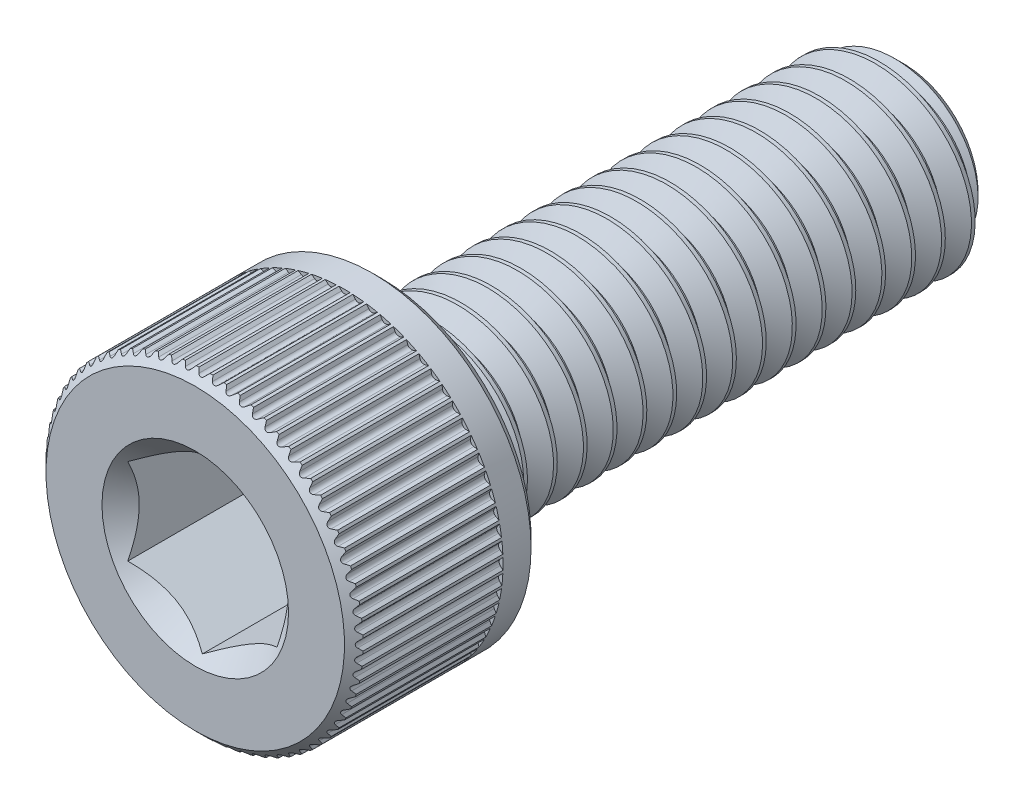
SolidWorks part; units mm, degrees
ref_plane "Front Plane" through (0, 0, 0) normal (0, 0, 1) x (1, 0, 0)
ref_plane "Top Plane" through (0, 0, 0) normal (0, 1, 0) x (1, 0, 0)
ref_plane "Right Plane" through (0, 0, 0) normal (1, 0, 0) x (0, 0, -1)
sketch "Sketch1" plane through (0, 0, 0) normal (1, 0, 0) x (0, 0, -1)
  line L0 (-9.5, 0) -> (9.5, 0) construction
  line L1 (9.5, 0) -> (9.5, 1.9804) construction
  line L2 (9.5, 1.9804) -> (8.9804, 2.5) construction
  line L3 (8.9804, 2.5) -> (8.9, 2.5) construction
  line L4 (8.9, 2.5) -> (-4.5, 2.5) construction
  line L5 (-4.5, 2.5) -> (-4.5, 4.25) construction
  line L6 (-4.5, 4.25) -> (-9.5, 4.25) construction
  line L7 (-9.5, 4.25) -> (-9.5, 0) construction
  line L8 (9.5, 1.9804) -> (9.5, 2.5) construction
  line L9 (9.45, 2.5866) -> (9.85, 1.8938) construction
  line L10 (9.85, 1.8938) -> (10.25, 2.5866) construction
  line L11 (10.25, 2.5866) -> (9.45, 2.5866) construction
  line L12 (9.85, 2.5866) -> (9.85, 2.5) construction
  line L13 (9.85, 1.8938) -> (9.85, 1.9804) construction
  line L14 (9.8, 1.9804) -> (9.9, 1.9804) construction
  line L15 (9.5, 2.5) -> (10.2, 2.5) construction
  line L16 (9.475, 2.5433) -> (10.225, 2.5433) construction
  line L17 (9.5, 0) -> (9.5, -2.5) construction
  line L18 (-4.75, 4.25) -> (-4.5, 4) construction
  line L19 (-9.25, 4.25) -> (-9.5, 4) construction
  line L20 (-4.5, 2.5) -> (-4.5, 0) construction
  line L21 (-4.5, 1.25) -> (0.1667, 1.25) construction
  line L22 (0.1667, 1.25) -> (4.8333, 1.25) construction
  line L23 (4.8333, 1.25) -> (9.5, 1.25) construction
  line L24 (0.1667, 1.25) -> (0.1667, 2.5) construction
  line L25 (0.1667, 2.5) -> (0.1667, 4.25) construction
  line L26 (4.8333, 1.25) -> (4.8333, 4.25) construction
  point P0 (-9.5, 2)
  point P3 (7.5, 2.5)
  point P4 (0, 0)
  point P18 (4.8333, 2.5)
  point P22 (9.85, 1.9804)
  point P24 (8.9, 2.5)
  point P25 (9.85, 2.5)
  point P28 (9.85, 2.5433)
  point P29 (7.5, -2.5)
  point P30 (0.1667, 2.5)
  point P31 (-7, 4.25)
  point P37 (-5.375, 4.25)
  point P38 (-9.125, 4.25)
  point P45 (0.1667, 1.25)
  point P46 (4.8333, 1.25)
  dimension "D7" = 0.25
  dimension "D8" = 0.25
  dimension "D9" = 0.25
  dimension "D10" = 0.125
  dimension "D11" = 0.625
  dimension "Drive Size" = 4
  dimension "Head Diameter" = 8.5
  dimension "Head Height" = 5
  dimension "Thread Pitch" = 0.8
  dimension "Thread Size" = 5
  dimension "Length" = 14
  dimension "D12" = 0.6
  dimension "D4" = 2
  dimension "D3" = 45
sketch "Sketch2" plane through (0, 0, 0) normal (1, 0, 0) x (0, 0, -1)
  line L0 (-9.5, 0) -> (-9.5, 4)
  line L1 (-9.25, 4.25) -> (-4.75, 4.25)
  line L2 (-4.5, 4) -> (-4.5, 2.75)
  line L4 (8.9804, 2.5) -> (9.5, 1.9804)
  line L5 (9.5, 1.9804) -> (9.5, 0)
  line L6 (-4.5, 4.25) -> (-9.5, 4.25) construction
  line L7 (9.5, 0) -> (-9.5, 0)
  line L8 (-9.25, 4.25) -> (-9.5, 4) construction
  line L10 (-9.25, 4.25) -> (-9.5, 4)
  line L14 (-4.75, 4.25) -> (-4.5, 4) construction
  line L16 (-4.75, 4.25) -> (-4.5, 4)
  line L17 (-4.5, 2.5) -> (-4.5, 4.25) construction
  line L19 (-4.25, 2.5) -> (8.9804, 2.5)
  line L20 (8.9, 2.5) -> (-4.5, 2.5) construction
  arc A1 (-4.5, 2.75) -> (-4.25, 2.5) centre (-4.25, 2.75) ccw
  dimension "D3" = 0.25
revolve "Revolve1" add sketch "Sketch2" angle 360 about L7
sketch "Sketch3" plane through (0, 0, 9.5) normal (0, 0, 1) x (1, 0, 0)
  line L1 (2, -1.1547) -> (2, 1.1547)
  line L2 (2, 1.1547) -> (0, 2.3094)
  line L3 (0, 2.3094) -> (-2, 1.1547)
  line L4 (-2, 1.1547) -> (-2, -1.1547)
  line L5 (-2, -1.1547) -> (0, -2.3094)
  line L6 (0, -2.3094) -> (2, -1.1547)
  circle A0 centre (0, 0) radius 2 construction
  circle A1 centre (0, 0) radius 4.25 construction
  circle A2 centre (0, 0) radius 4.25 construction
  circle A3 centre (0, 0) radius 2.3094 construction
  point P13 (0, 0)
extrude "Cut-Extrude1" cut sketch "Sketch3" against normal offset from surface (4 mm away) 1 up to face at (0, 4, 4.5)
sketch "Sketch4" plane through (0, 0, 9.5) normal (0, 0, 1) x (1, 0, 0)
  circle A0 centre (0, 0) radius 2.5
  dimension "D1" = 5
extrude "Cut-Extrude2" cut sketch "Sketch4" against normal up to vertex (2.5 mm away) draft 45 up to point (0, 4.25, 7)
sketch "Sketch11" plane through (0, 0, 0) normal (1, 0, 0) x (0, 0, -1)
  line L0 (-9.5, 0) -> (9.5, 0) construction
  line L1 (-9.5, 0) -> (9.5, 0) construction
  line L2 (-1.875, 0) -> (-1.875, 2.5) construction
  line L3 (8.9, 2.5) -> (-4.5, 2.5) construction
  line L4 (6.875, 0) -> (6.875, 2.5) construction
  line L6 (9.5, 1.9804) -> (9.5, 2.5) construction
  point P2 (-1.875, 0)
  point P3 (6.875, 0)
  dimension "D1" = 2.625
  dimension "D2" = 2.625
sketch "Sketch6" plane through (0, 0, -9.5) normal (0, 0, -1) x (-1, 0, 0)
  circle A0 centre (0, 0) radius 2.5
curve "Helix/Spiral1" pitch 0.8 height 14.8 radius 2.5 centre (0, 0, -9.5) axis (0, 0, 1) start towards (0, 1, 0)
sketch "Sketch10" plane through (0, 0, 0) normal (1, 0, 0) x (0, 0, -1)
  line L0 (-4.25, -4.25) -> (-4.25, 4.25)
  line L5 (-9.5, 0) -> (9.5, 0) construction
  line L6 (-4.25, 2.5) -> (-4.25, -2.5) construction
  point P3 (-4.25, 0)
split "Split1" trim tools "Sketch10" bodies to split 106 resulting bodies 114 115
sketch "Sketch7" plane through (0, 0, 0) normal (1, 0, 0) x (0, 0, -1)
  line L0 (9.475, 2.5433) -> (10.225, 2.5433)
  line L1 (10.225, 2.5433) -> (9.9, 1.9804)
  line L2 (9.9, 1.9804) -> (9.8, 1.9804)
  line L3 (9.8, 1.9804) -> (9.475, 2.5433)
sweep "Cut-Sweep1" cut profiles "Sketch7" path "Helix/Spiral1" align with end faces yes
sketch "Sketch8" plane through (0, 0, 0) normal (1, 0, 0) x (0, 0, -1)
  line L0 (-4.5, 0) -> (-4.5, 2.5)
  line L1 (-4.25, -2.5) -> (-4.25, 2.5) construction
  line L2 (-4.5, 2.5) -> (-4.25, 2.5)
  line L4 (-4.25, 2.5) -> (-2.8066, 0)
  line L5 (-2.8066, 0) -> (-4.5, 0)
  line L6 (8.9, 2.5) -> (-4.5, 2.5) construction
  line L7 (-9.5, 0) -> (9.5, 0) construction
  dimension "D1" = 60
revolve "Revolve2" add sketch "Sketch8" angle 360 about L5
ref_plane "Plane1" through (0, 0, 9.5) normal (0, 0, 1) x (1, 0, 0)
sketch "Sketch12" plane through (0, 0, 9.5) normal (0, 0, 1) x (1, 0, 0)
  line L0 (0, 0) -> (0.1483, 4.2474) construction
  line L1 (0, 0) -> (-0.1483, 4.2474) construction
  line L2 (0, 4.1437) -> (0, 4.3563) construction
  line L3 (-0.2572, 4.3563) -> (0.2572, 4.3563)
  line L4 (-0.2572, 4.3563) -> (-0.0762, 4.1753)
  line L5 (0.0762, 4.1753) -> (0.2572, 4.3563)
  circle A0 centre (0, 0) radius 4.25 construction
  arc A1 (-0.0762, 4.1753) -> (0.0762, 4.1753) centre (0, 4.2516) ccw
  point P9 (0, 4.3563)
  point P13 (0, 4.25)
  dimension "D1" = 4
  dimension "D2" = 0.1063
extrude "Cut-Extrude3" cut sketch "Sketch12" against normal blind 4
pattern_circular "CirPattern1" count 72 over 360 about axis through (0, 0, 9.5) along (0, 0, -1) of "Cut-Extrude3"
equation "\"D2@Sketch1\" = \"Thread Pitch@Sketch1\" / 8"
equation "\"D4@Helix/Spiral1\" = \"Thread Pitch@Sketch1\""
equation "\"D7@Sketch1\" = \"Head Height@Sketch1\" * .05"
equation "\"D8@Sketch1\"=\"D7@Sketch1\""
equation "\"D9@Sketch1\"=\"D7@Sketch1\""
equation "\"D10@Sketch1\"=\"D7@Sketch1\"/2"
equation "\"D11@Sketch1\"=\"D10@Sketch1\"*5"
equation "\"D4@Sketch1\"=\"Thread Pitch@Sketch1\"*2.5"
equation "\"D12@Sketch1\"=\"Thread Pitch@Sketch1\"*.75"
equation "\"D3@Helix/Spiral1\"=\"Length@Sketch1\"+\"Thread Pitch@Sketch1\""
equation "\"D3@Sketch2\" = \"Thread Size@Sketch1\" * 0.05"
equation "\"D1@Sketch11\"=\"Length@Sketch1\"*0.1875"
equation "\"D2@Sketch11\"=\"D1@Sketch11\""
equation "\"D2@Sketch12\"=\"Head Diameter@Sketch1\"*.0125"
equation "\"D1@Cut-Extrude3\"=\"Head Height@Sketch1\"*.8"
equation "\"D1@CirPattern1\"=\"D3@CirPattern1\"/(1.25*\"D1@Sketch12\")"
equation "\"D1@Sketch4\"=\"Drive Size@Sketch1\"*1.25"
